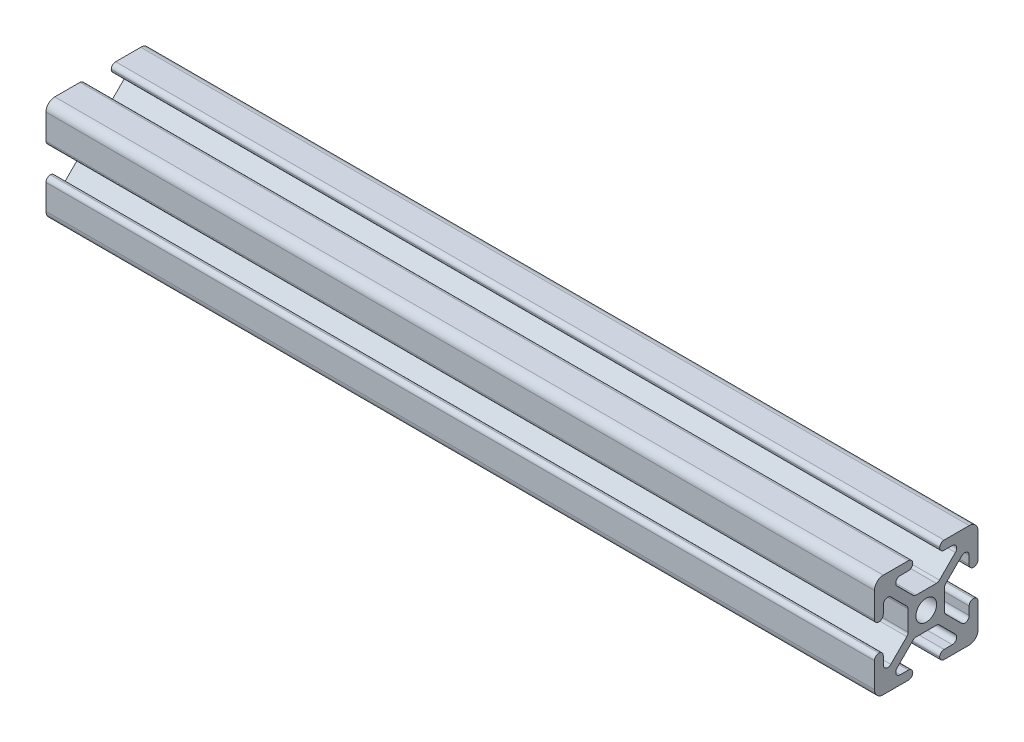
SolidWorks part; units mm, degrees
ref_plane "Front Plane" through (0, 0, 0) normal (1, 0, 0) x (0, 1, 0)
ref_plane "Top Plane" through (0, 0, 0) normal (0, 0, 1) x (0, 1, 0)
ref_plane "Right Plane" through (0, 0, 0) normal (0, 1, 0) x (-1, 0, 0)
sketch "Sketch1" plane through (0, 0, 0) normal (1, 0, 0) x (0, 1, 0)
  line L0 (0, 0) -> (0, 12.5) construction
  line L1 (-12.5, -12.5) -> (12.5, -12.5)
  line L2 (-12.5, -12.5) -> (-12.5, 12.5)
  line L3 (-12.5, 12.5) -> (12.5, 12.5)
  line L4 (12.5, -12.5) -> (12.5, 12.5)
  line L5 (-12.5, -12.5) -> (12.5, 12.5) construction
  line L6 (-12.5, 12.5) -> (12.5, -12.5) construction
  line L7 (-3.25, 12.5) -> (-3.25, 10.37)
  line L8 (-3.25, 10.37) -> (-8.8639, 10.37)
  line L9 (-8.8639, 10.37) -> (-2.8739, 4.38)
  line L10 (-2.8739, 4.38) -> (2.8739, 4.38)
  line L11 (8.8639, 10.37) -> (2.8739, 4.38)
  line L12 (3.25, 10.37) -> (8.8639, 10.37)
  line L13 (3.25, 12.5) -> (3.25, 10.37)
  line L14 (12.5, -3.25) -> (10.37, -3.25)
  line L15 (10.37, -3.25) -> (10.37, -8.8639)
  line L16 (10.37, -8.8639) -> (4.38, -2.8739)
  line L17 (4.38, 2.8739) -> (4.38, -2.8739)
  line L18 (10.37, 8.8639) -> (4.38, 2.8739)
  line L19 (10.37, 3.25) -> (10.37, 8.8639)
  line L20 (12.5, 3.25) -> (10.37, 3.25)
  line L21 (-3.25, -12.5) -> (-3.25, -10.37)
  line L22 (-3.25, -10.37) -> (-8.8639, -10.37)
  line L23 (-8.8639, -10.37) -> (-2.8739, -4.38)
  line L24 (2.8739, -4.38) -> (-2.8739, -4.38)
  line L25 (8.8639, -10.37) -> (2.8739, -4.38)
  line L26 (3.25, -10.37) -> (8.8639, -10.37)
  line L27 (3.25, -12.5) -> (3.25, -10.37)
  line L28 (-12.5, 3.25) -> (-10.37, 3.25)
  line L29 (-10.37, 3.25) -> (-10.37, 8.8639)
  line L30 (-10.37, 8.8639) -> (-4.38, 2.8739)
  line L31 (-4.38, -2.8739) -> (-4.38, 2.8739)
  line L32 (-10.37, -8.8639) -> (-4.38, -2.8739)
  line L33 (-10.37, -3.25) -> (-10.37, -8.8639)
  line L34 (-12.5, -3.25) -> (-10.37, -3.25)
  circle A0 centre (0, 0) radius 2.5
  point P0 (0, 0)
  point P15 (0, 4.38)
  dimension "D3" = 5
  dimension "D1" = 25
  dimension "D2" = 25
  dimension "D4" = 2.13
  dimension "D5" = 2.13
  dimension "D6" = 6.5
  dimension "D7" = 4.38
  dimension "D8" = 4
extrude "Boss-Extrude1" add sketch "Sketch1" along normal blind 200 contours L34 L2 L1 L21 L22 L23 L24 L25 L26 L27 L4 L14 L15 L16 L17 L18 L19 L20 L3 L13 L12 L11 L10 L9 L8 L7 L28 L29 L30 L31 L32 L33 A0 region at (0, -12.1464, -7.875)
fillet "Fillet1" radius 1.065 32 edges at (100, -10.37, -8.8639) (100, 2.8739, -4.38) (100, -2.8739, -4.38) (100, -4.38, 2.8739) (100, -4.38, -2.8739) (100, -2.8739, 4.38) (100, 2.8739, 4.38) (100, 4.38, 2.8739) (100, 4.38, -2.8739) (100, -8.8639, -10.37) (100, 8.8639, -10.37) (100, 10.37, -8.8639) (100, -10.37, 8.8639) (100, -8.8639, 10.37) (100, 10.37, 8.8639) (100, 8.8639, 10.37) (100, 12.5, 3.25) (100, -3.25, -12.5) (100, -10.37, 3.25) (100, 10.37, 3.25) (100, -10.37, -3.25) (100, -12.5, -3.25) (100, -12.5, 3.25) (100, 3.25, -10.37) (100, -3.25, -10.37) (100, 3.25, -12.5) (100, 10.37, -3.25) (100, 12.5, -3.25) (100, 3.25, 12.5) (100, 3.25, 10.37) (100, -3.25, 10.37) (100, -3.25, 12.5)
fillet "Fillet2" radius 2.13 4 edges at (100, 12.5, -12.5) (100, -12.5, -12.5) (100, 12.5, 12.5) (100, -12.5, 12.5)
